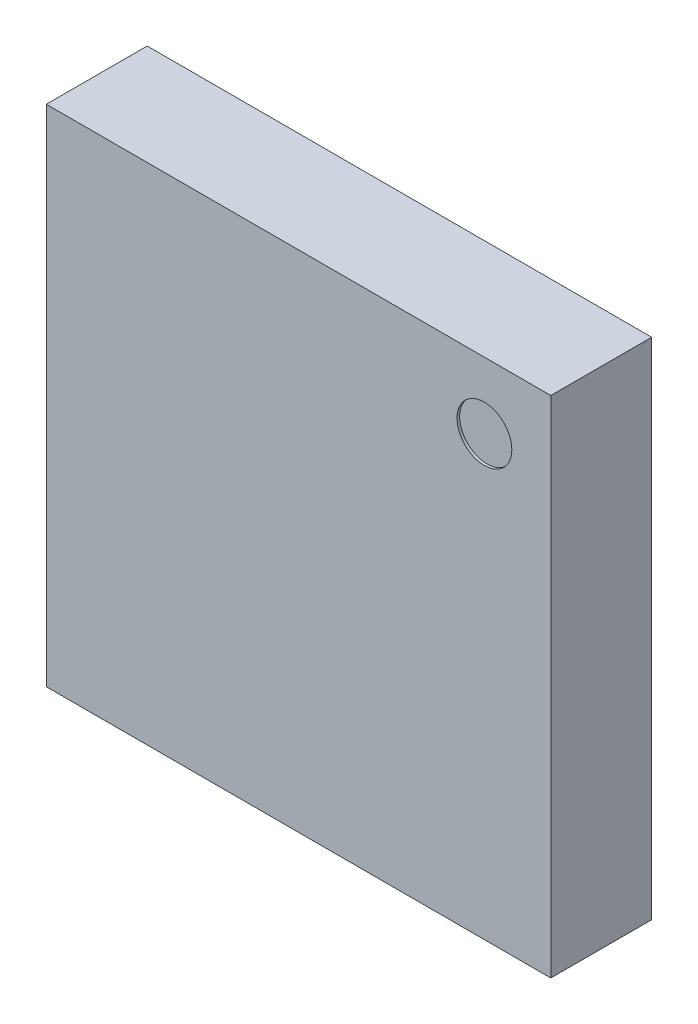
SolidWorks part; units mm, degrees
ref_plane "Front Plane" through (0, 0, 0) normal (0, 0, 1) x (1, 0, 0)
ref_plane "Top Plane" through (0, 0, 0) normal (0, 1, 0) x (1, 0, 0)
ref_plane "Right Plane" through (0, 0, 0) normal (1, 0, 0) x (0, 0, -1)
sketch "Sketch1" plane through (0, 0, 0) normal (0, 0, 1) x (1, 0, 0)
  line L1 (-0.95, 0.95) -> (0.95, 0.95)
  line L2 (-0.95, 0.95) -> (-0.95, -0.95)
  line L3 (-0.95, -0.95) -> (0.95, -0.95)
  line L4 (0.95, 0.95) -> (0.95, -0.95)
  line L5 (-0.95, 0.95) -> (0.95, -0.95) construction
  line L6 (-0.95, -0.95) -> (0.95, 0.95) construction
  point P0 (0, 0)
  dimension "D1" = 1.9
  dimension "D2" = 1.9
extrude "Boss-Extrude1" add sketch "Sketch1" along normal blind 0.38
sketch "Sketch2" plane through (0, 0, 0) normal (0, 0, -1) x (-1, 0, 0)
  circle A0 centre (0.75, 0.75) radius 0.125
  circle A1 centre (0.25, 0.75) radius 0.125
  circle A2 centre (-0.25, 0.75) radius 0.125
  circle A3 centre (-0.75, 0.75) radius 0.125
  circle A6 centre (-0.75, 0.25) radius 0.125
  circle A7 centre (0.25, -0.25) radius 0.125
  circle A8 centre (-0.25, -0.25) radius 0.125
  circle A9 centre (-0.75, -0.25) radius 0.125
  circle A10 centre (0.25, -0.75) radius 0.125
  circle A11 centre (-0.25, -0.75) radius 0.125
  circle A12 centre (-0.75, -0.75) radius 0.125
  circle A13 centre (0.75, 0.25) radius 0.125
  circle A14 centre (0.75, -0.25) radius 0.125
  circle A15 centre (0.75, -0.75) radius 0.125
  circle A16 centre (-0.25, 0.25) radius 0.125 [skipped]
  circle A17 centre (0.25, 0.25) radius 0.125 [skipped]
  dimension "D1" = 0.75
  dimension "D3" = 0.25
  dimension "D2" = 0.75
  dimension "D4" = 4
  dimension "D5" = 4
extrude "Boss-Extrude2" add sketch "Sketch2" along normal blind 0.125
fillet "Fillet1" radius 0.125 14 edges at (-0.875, -0.75, -0.125) (-0.375, -0.75, -0.125) (0.125, -0.75, -0.125) (0.125, -0.25, -0.125) (-0.375, -0.25, -0.125) (-0.875, -0.25, -0.125) (-0.875, 0.25, -0.125) (-0.875, 0.75, -0.125) (-0.375, 0.75, -0.125) (0.125, 0.75, -0.125) (0.625, 0.75, -0.125) (0.625, 0.25, -0.125) (0.625, -0.25, -0.125) (0.625, -0.75, -0.125)
sketch "Sketch3" plane through (0, 0, 0.38) normal (0, 0, 1) x (1, 0, 0)
  circle A0 centre (0.7, 0.7) radius 0.1032
  dimension "D1" = 0.7
  dimension "D2" = 0.7
extrude "Cut-Extrude1" cut sketch "Sketch3" against normal blind 0.01
